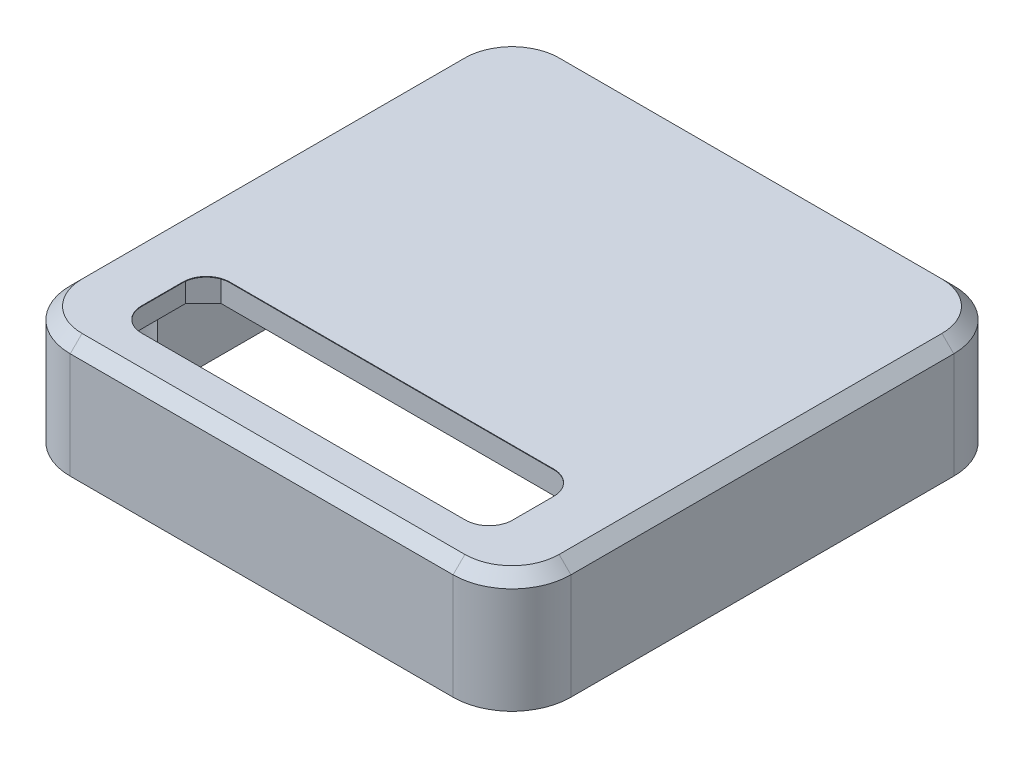
SolidWorks part; units mm, degrees
ref_plane "Front Plane" through (0, 0, 0) normal (0, 0, 1) x (1, 0, 0)
ref_plane "Top Plane" through (0, 0, 0) normal (0, 1, 0) x (1, 0, 0)
ref_plane "Right Plane" through (0, 0, 0) normal (1, 0, 0) x (0, 0, -1)
sketch "Sketch1" plane through (0, 0, 0) normal (0, 1, 0) x (1, 0, 0)
  line L1 (-42.5, -42.5) -> (42.5, -42.5)
  line L2 (-42.5, -42.5) -> (-42.5, 42.5)
  line L3 (-42.5, 42.5) -> (42.5, 42.5)
  line L4 (42.5, -42.5) -> (42.5, 42.5)
  line L5 (-42.5, -42.5) -> (42.5, 42.5) construction
  line L6 (-42.5, 42.5) -> (42.5, -42.5) construction
  point P0 (0, 0)
  dimension "D1" = 85
extrude "Boss-Extrude1" add sketch "Sketch1" along normal blind 20
fillet "Fillet1" radius 10 4 edges at (-42.5, 10, -42.5) (42.5, 10, -42.5) (42.5, 10, 42.5) (-42.5, 10, 42.5)
chamfer "Chamfer1" distance 2 angle 45 8 edges at (39.5711, 20, -39.5711) (42.5, 20, 0) (39.5711, 20, 39.5711) (0, 20, 42.5) (-39.5711, 20, 39.5711) (-42.5, 20, 0) (-39.5711, 20, -39.5711) (0, 20, -42.5)
shell "Shell2" thickness 5 removed face at (0, 0, 0)
sketch "Sketch2" plane through (0, 20, 0) normal (0, 1, 0) x (1, 0, 0)
  line L0 (-32.5, -40.5) -> (32.5, -40.5) construction
  line L1 (-30.1, -36.5) -> (30.1, -36.5)
  line L2 (-33.1, -33.5) -> (-33.1, -22.3)
  line L3 (-30.1, -19.3) -> (30.1, -19.3)
  line L4 (33.1, -33.5) -> (33.1, -22.3)
  line L5 (-33.1, -36.5) -> (33.1, -19.3) construction
  line L6 (-33.1, -19.3) -> (33.1, -36.5) construction
  line L7 (-33.1, -22.3) -> (-30.1, -19.3)
  line L8 (-33.1, -33.5) -> (-30.1, -36.5)
  line L9 (30.1, -19.3) -> (33.1, -22.3)
  line L10 (30.1, -36.5) -> (33.1, -33.5)
  point P0 (0, -27.9)
  point P5 (0, 0)
  dimension "D1" = 17.2
  dimension "D2" = 66.2
  dimension "D3" = 4
extrude "Cut-Extrude1" cut sketch "Sketch2" against normal through all
sketch "Sketch3" plane through (0, 15, 0) normal (0, -1, 0) x (1, 0, 0)
  line L2 (-30.1, 19.3) -> (30.1, 19.3) construction
  line L3 (7.5, 6.3) -> (-7.5, 6.3)
  line L4 (7.5, 6.3) -> (7.5, -35.5)
  line L5 (7.5, -35.5) -> (-7.5, -35.5)
  line L6 (-7.5, 6.3) -> (-7.5, -35.5)
  line L7 (32.5, -37.5) -> (-32.5, -37.5) construction
  circle A0 centre (3, 10.3) radius 2
  circle A1 centre (-3, 10.3) radius 2
  dimension "D5" = 9
  dimension "D6" = 9
  dimension "D7" = 4
  dimension "D8" = 4
  dimension "D1" = 13
  dimension "D2" = 2
  dimension "D3" = 15
  dimension "D4" = 7.5
  dimension "D9" = 3
  dimension "D10" = 3
extrude "Cut-Extrude2" cut sketch "Sketch3" against normal blind 2 contours L3 L6 L5 L4 region at (0, 15, -14.6)
extrude "Cut-Extrude3" cut sketch "Sketch3<4>" against normal blind 4 contours A1 | A0 region at (3, 15, 10.3) region at (-3, 15, 10.3)
sketch "Sketch3<4>" plane through (0, 15, 0) normal (0, -1, 0) x (1, 0, 0) same geometry as "Sketch3"
sketch "Sketch4" plane through (0, 20, 0) normal (0, 1, 0) x (1, 0, 0)
  line L0 (30.1, -19.3) -> (-30.1, -19.3) construction
  line L1 (-27.5, -35.4) -> (27.5, -35.4)
  line L2 (-31.5, -31.4) -> (-31.5, -24.4)
  line L3 (-27.5, -20.4) -> (27.5, -20.4)
  line L4 (31.5, -31.4) -> (31.5, -24.4)
  line L5 (-31.5, -35.4) -> (31.5, -20.4) construction
  line L6 (-31.5, -20.4) -> (31.5, -35.4) construction
  arc A0 (-27.5, -35.4) -> (-31.5, -31.4) centre (-27.5, -31.4) cw
  arc A1 (27.5, -35.4) -> (31.5, -31.4) centre (27.5, -31.4) ccw
  arc A2 (27.5, -20.4) -> (31.5, -24.4) centre (27.5, -24.4) cw
  arc A3 (-31.5, -24.4) -> (-27.5, -20.4) centre (-27.5, -24.4) cw
  point P0 (0, -27.9)
  point P7 (0, 0)
  line M5 (-33.1, -33.5) -> (-33.1, -22.3)
  line M6 (-33.1, -22.3) -> (-30.1, -19.3)
  line M7 (-30.1, -19.3) -> (30.1, -19.3)
  line M8 (30.1, -19.3) -> (33.1, -22.3)
  line M9 (33.1, -22.3) -> (33.1, -33.5)
  line M10 (33.1, -33.5) -> (30.1, -36.5)
  line M11 (30.1, -36.5) -> (-30.1, -36.5)
  line M12 (-30.1, -36.5) -> (-33.1, -33.5)
  dimension "D4" = 4
  dimension "D1" = 8.6
  dimension "D2" = 15
  dimension "D3" = 63
extrude "Boss-Extrude2" add sketch "Sketch4" against normal blind 0.1 contours L2 A3 L3 A2 L4 A1 L1 A0 M5 M12 M11 M10 M9 M8 M7 M6 region at (-32.416, 20, 27.9)
sketch "Sketch5" plane through (0, 0, 0) normal (0, -1, 0) x (1, 0, 0)
  line L0 (33.1, 22.3) -> (33.1, 33.5) construction
  line L1 (-35.75, 22.4) -> (35.75, 22.4)
  line L2 (-35.75, 22.4) -> (-35.75, 33.4)
  line L3 (-35.75, 33.4) -> (35.75, 33.4)
  line L4 (35.75, 22.4) -> (35.75, 33.4)
  arc A0 (-35.75, 33.4) -> (-35.75, 22.4) centre (-35.75, 27.9) ccw
  arc A1 (35.75, 33.4) -> (35.75, 22.4) centre (35.75, 27.9) cw
  point P6 (0, 0)
  point P11 (33.1, 27.9)
  line M13 (-37.5, -32.5) -> (-37.5, 32.5)
  arc M14 (-37.5, 32.5) -> (-32.5, 37.5) centre (-32.5, 32.5) cw
  arc M16 (32.5, 37.5) -> (37.5, 32.5) centre (32.5, 32.5) cw
  line M17 (37.5, 32.5) -> (37.5, -32.5)
  dimension "D1" = 82.5
  dimension "D3" = 35.75
  dimension "D2" = 11
extrude "Cut-Extrude9" cut sketch "Sketch5" against normal up to surface (15 mm away) contours A0 M14 M13 | A1 M16 M17 region at (-39.0544, 0, 27.9014) region at (39.0544, 0, 27.9014) up to face at (-3, 15, 8.3)
sketch "Sketch17" plane through (0, 0, 37.5) normal (0, 0, -1) x (-1, 0, 0)
  line L0 (-32.5, 15) -> (32.5, 15) construction
  line L1 (-20, 15) -> (-10, 15)
  line L2 (-20, 15) -> (-20, 14)
  line L3 (-20, 14) -> (-10, 14)
  line L4 (-10, 15) -> (-10, 14)
  line L5 (0, 11) -> (0, -11) construction
  line L6 (10, 15) -> (10, 14)
  line L7 (20, 14) -> (10, 14)
  line L8 (20, 15) -> (20, 14)
  line L9 (20, 15) -> (10, 15)
  line L11 (20, 15) -> (32.4605, 15)
  line L12 (32.4605, 15) -> (32.4605, 14)
  line L13 (32.4605, 14) -> (20, 14)
  line L14 (37.4605, 15) -> (37.4605, 0) construction
  line L15 (22.4605, 15) -> (22.4605, 14)
  line L16 (-32.4605, 15) -> (-32.4605, 14)
  line L17 (-32.4605, 14) -> (-20, 14)
  line L18 (-22.4605, 15) -> (-22.4605, 14)
  line L19 (-20, 15) -> (-32.4605, 15)
  line M8 (32.5, 15) -> (-32.5, 15)
  dimension "D1" = 1
  dimension "D2" = 10
  dimension "D3" = 10
  dimension "D4" = 5
  dimension "D5" = 10
extrude "Cut-Extrude10" cut sketch "Sketch17" against normal blind 2 contours L18 L16 L17 M8 | L8 L6 L7 M8 region at (-15, 14.5, 37.5) region at (27.4605, 14.5, 37.5)
chamfer "Chamfer4" distance 2 angle 45 2 edges at (-15, 14, 37.5) (27.4605, 14, 37.5)
sketch "Sketch18" plane through (0, 15, 0) normal (0, -1, 0) x (1, 0, 0)
  circle A0 centre (-17.5, 15) radius 2
  circle A2 centre (29.9605, 15) radius 2
  point P5 (0, 0)
  dimension "D2" = 4
  dimension "D1" = 2.5
  dimension "D3" = 22.5
  dimension "D4" = 2.5
extrude "Cut-Extrude11" cut sketch "Sketch18" against normal blind 3
sketch "Sketch19" plane through (0, 15, 0) normal (0, -1, 0) x (1, 0, 0)
  line L0 (-30.1, 19.3) -> (30.1, 19.3) construction
  line L1 (-6.05, 13.8) -> (6.05, 13.8)
  line L2 (-6.05, 13.8) -> (-6.05, 16.8)
  line L3 (-6.05, 16.8) -> (6.05, 16.8)
  line L4 (6.05, 13.8) -> (6.05, 16.8)
  line L5 (-6.05, 13.8) -> (6.05, 16.8) construction
  line L6 (-6.05, 16.8) -> (6.05, 13.8) construction
  line L9 (-6.05, 13.8) -> (-6.05, 6.3)
  line L10 (7.5, 6.3) -> (-7.5, 6.3) construction
  line L11 (6.05, 13.8) -> (6.05, 6.3)
  line L12 (-9.05, 6.3) -> (-9.05, 16.8)
  line L13 (9.05, 6.3) -> (9.05, 16.8)
  line L14 (9.05, 16.8) -> (6.05, 16.8)
  line L15 (-9.05, 16.8) -> (-6.05, 16.8)
  line L16 (-9.05, 6.3) -> (-6.05, 6.3)
  line L17 (6.05, 6.3) -> (9.05, 6.3)
  point P0 (0, 15.3)
  line M27 (-7.5, 6.3) -> (7.5, 6.3)
  dimension "D1" = 5.5
  dimension "D2" = 3
  dimension "D3" = 12.1
  dimension "D4" = 3
  dimension "D5" = 3
extrude "Boss-Extrude8" add sketch "Sketch19" along normal blind 2.5 contours L15 L12 L9 L2 M27 | L13 L14 L4 L11 M27 | L1 L4 L3 L2 region at (0, 15, 15.3) region at (-7.55, 15, 11.55) region at (7.55, 15, 11.55)
sketch "Sketch20" plane through (0, 15, 0) normal (0, -1, 0) x (1, 0, 0)
  line L0 (-10, -32.5) -> (-10, -2.5)
  line L1 (-10, -32.5) -> (-32.5, -32.5)
  line L2 (-32.5, -32.5) -> (-32.5, -2.5)
  line L3 (-10, -2.5) -> (-32.5, -2.5)
  line L4 (-10, -32.5) -> (-32.5, -2.5) construction
  line L5 (-32.5, -32.5) -> (-10, -2.5) construction
  line L6 (32.5, -37.5) -> (-32.5, -37.5) construction
  line L7 (-37.5, -32.5) -> (-37.5, 22.6858) construction
  line L8 (-21.25, -17.5) -> (-21.25, -2.5) construction
  circle A0 centre (-30.4, -30.4) radius 2
  circle A1 centre (-12.1, -4.6) radius 2
  circle A2 centre (-12.1, -30.4) radius 2
  circle A3 centre (-30.4, -4.6) radius 2
  point P0 (-21.25, -17.5)
  dimension "D1" = 4
  dimension "D2" = 2.1
  dimension "D3" = 2.1
  dimension "D6" = 2.1
  dimension "D7" = 4
  dimension "D8" = 2.1
  dimension "D4" = 30
  dimension "D5" = 22.5
  dimension "D9" = 5
  dimension "D10" = 5
extrude "Cut-Extrude12" cut sketch "Sketch20" against normal blind 4 contours A3 | A2 region at (-12.1, 15, -30.4) region at (-30.4, 15, -4.6)
